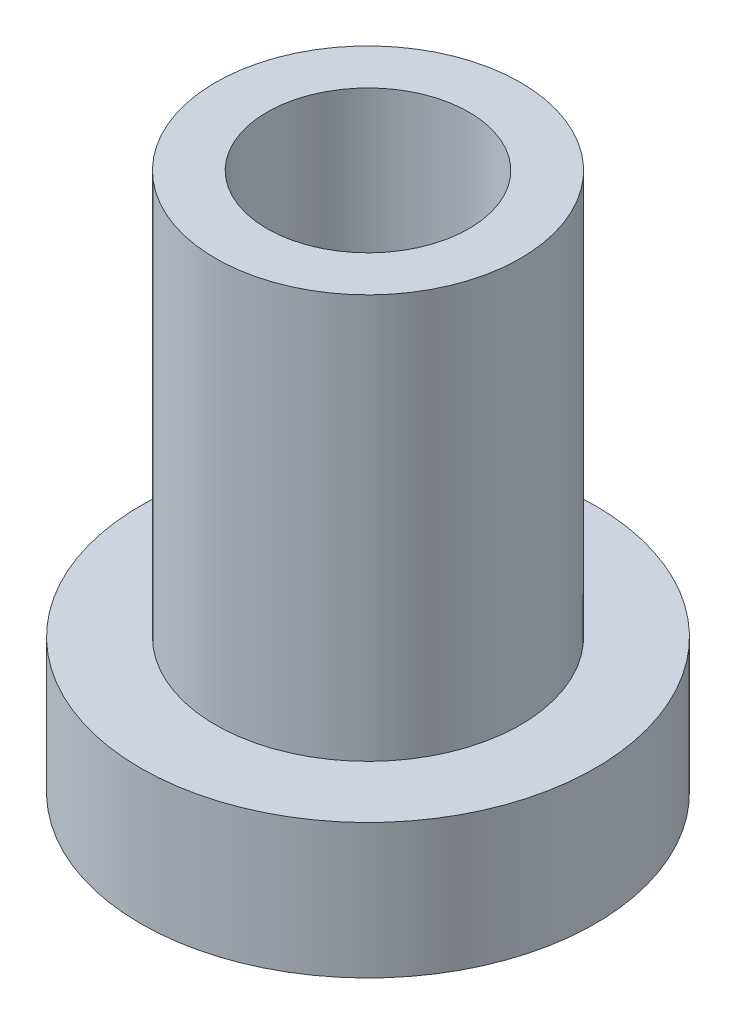
SolidWorks part; units mm, degrees
material "6061 Alloy"
ref_plane "Front Plane" through (0, 0, 0) normal (0, 0, 1) x (1, 0, 0)
ref_plane "Top Plane" through (0, 0, 0) normal (0, 1, 0) x (1, 0, 0)
ref_plane "Right Plane" through (0, 0, 0) normal (1, 0, 0) x (0, 0, -1)
sketch "Sketch1" plane through (0, 0, 0) normal (0, 1, 0) x (1, 0, 0)
  circle A0 centre (0, 0) radius 5.3594
  dimension "D1" = 10.7188
extrude "Boss-Extrude1" add sketch "Sketch1" along normal blind 3.175
sketch "Sketch2" plane through (0, 3.175, 0) normal (0, 1, 0) x (1, 0, 0)
  circle A1 centre (0, 0) radius 3.5941
  dimension "D2" = 7.1882
extrude "Boss-Extrude2" add sketch "Sketch2" along normal blind 9.525 contours A1 region at (0, 3.175, 0)
sketch "Sketch3" plane through (0, 12.7, 0) normal (0, 1, 0) x (1, 0, 0)
  circle A0 centre (0, 0) radius 2.3813
  dimension "D1" = 4.7625
extrude "Cut-Extrude1" cut sketch "Sketch3" against normal up to surface (12.7 mm away) contours A0 region at (0, 12.7, 0) up to face at (0, 0, 5.3594)
